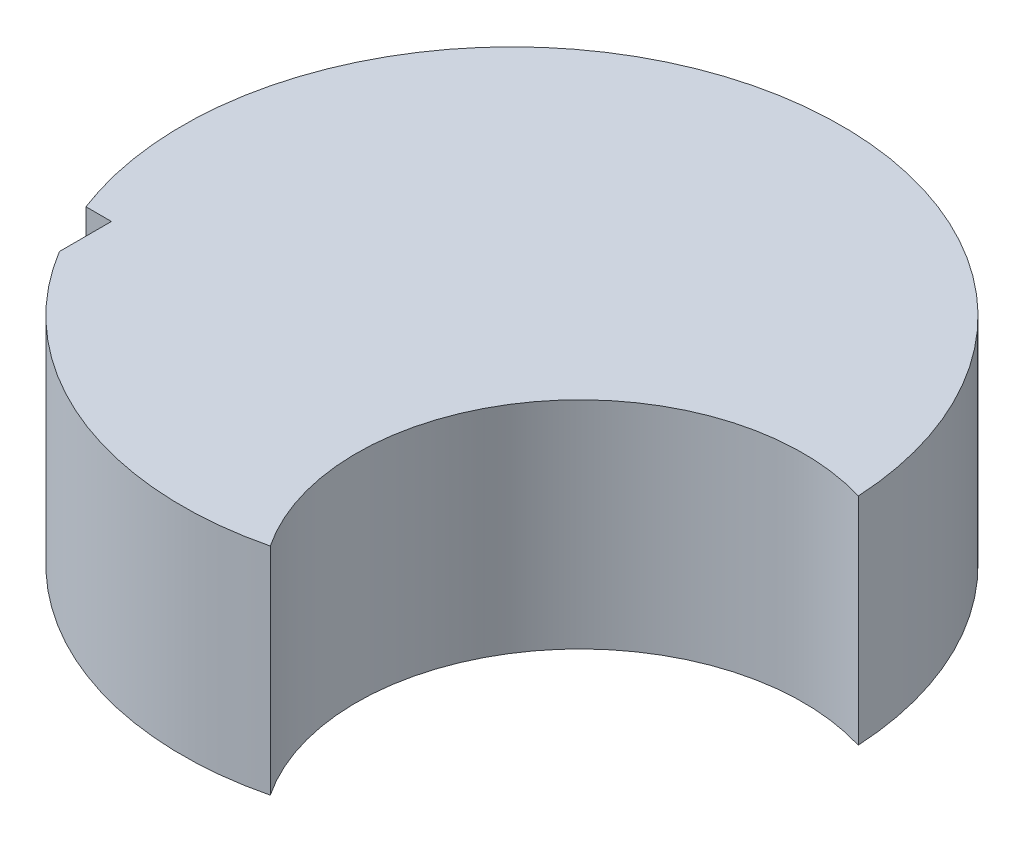
SolidWorks part; units mm, degrees
ref_plane "Front Plane" through (0, 0, 0) normal (0, 0, 1) x (1, 0, 0)
ref_plane "Top Plane" through (0, 0, 0) normal (0, 1, 0) x (1, 0, 0)
ref_plane "Right Plane" through (0, 0, 0) normal (1, 0, 0) x (0, 0, -1)
sketch "Sketch1" plane through (0, 0, 0) normal (0, 1, 0) x (1, 0, 0)
  arc A0 (92.9761, 4.8609) -> (22.1523, -90.4293) centre (0, 0) ccw
  arc A1 (92.9761, 4.8609) -> (22.1523, -90.4293) centre (74.7241, -55.5382) ccw
extrude "Boss-Extrude1" add sketch "Sketch1" along normal blind 60.96
ref_plane "Plane1" through (0, 137.16, 0) normal (0, 1, 0) x (1, 0, 0)
sketch "Sketch2" plane through (0, 137.16, 0) normal (0, 1, 0) x (1, 0, 0)
  point P0 (36.5712, 50.7694)
sketch "Sketch3" plane through (0, 60.96, 0) normal (0, 1, 0) x (1, 0, 0)
  line L1 (-120.6407, -33.4616) -> (-79.6791, -33.4616)
  line L2 (-120.6407, -33.4616) -> (-120.6407, -67.2117)
  line L3 (-120.6407, -67.2117) -> (-79.6791, -67.2117)
  line L4 (-79.6791, -33.4616) -> (-79.6791, -67.2117)
extrude "Cut-Extrude1" cut sketch "Sketch3" against normal up to next
ref_axis "Axis1" through (36.5712, 137.16, -50.7694) along (0, 1, 0)
